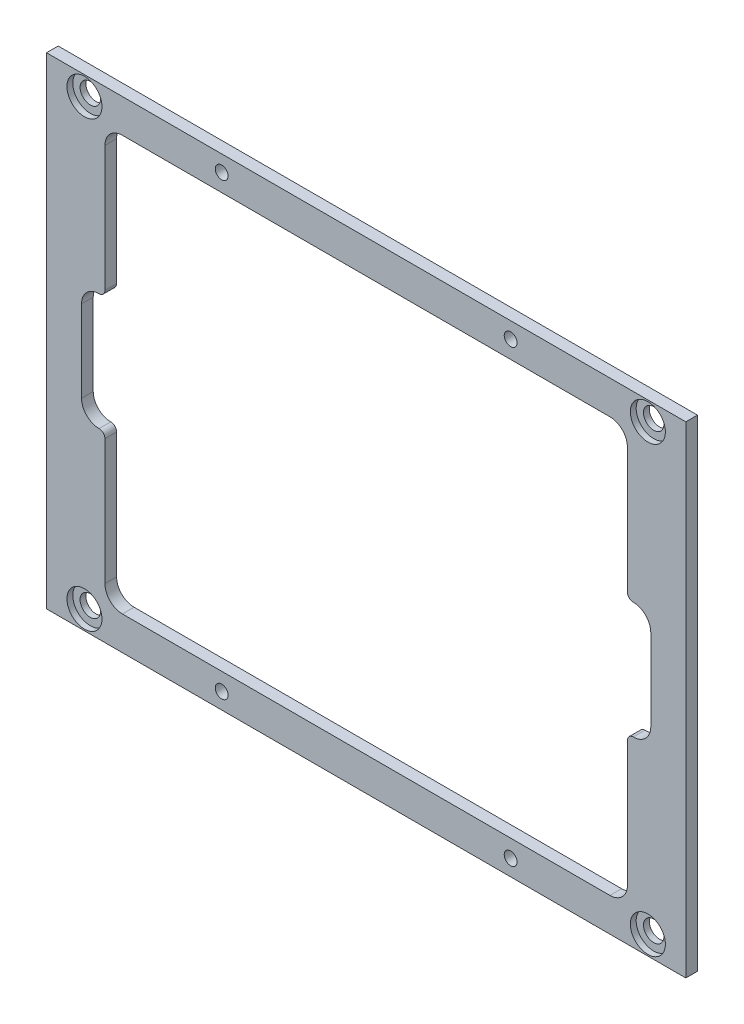
SolidWorks part; units mm, degrees
ref_plane "Front Plane" through (0, 0, 0) normal (0, 0, 1) x (1, 0, 0)
ref_plane "Top Plane" through (0, 0, 0) normal (0, 1, 0) x (1, 0, 0)
ref_plane "Right Plane" through (0, 0, 0) normal (1, 0, 0) x (0, 0, -1)
sketch "Sketch1" plane through (0, 0, 7.4347) normal (0, 0, 1) x (1, 0, 0)
  line L0 (-45.4936, 34.7019) -> (-49.4936, 34.7019)
  line L1 (-55.4936, 3.4519) -> (54.0064, 3.4519)
  line L2 (-55.4936, 3.4519) -> (-55.4936, 85.9519)
  line L3 (-55.4936, 85.9519) -> (54.0064, 85.9519)
  line L4 (54.0064, 3.4519) -> (54.0064, 85.9519)
  line L5 (55.0064, 3.4519) -> (-56.4936, 3.4519) construction
  line L6 (-49.4936, 34.7019) -> (-49.4936, 54.7019)
  line L7 (-42.4936, 80.2019) -> (41.0064, 80.2019)
  line L8 (-45.4936, 77.2019) -> (-45.4936, 54.7019)
  line L9 (-42.4936, 9.2019) -> (41.0064, 9.2019)
  line L10 (44.0064, 77.2019) -> (44.0064, 54.7019)
  line L11 (54.0064, 44.7019) -> (44.0064, 44.7019) construction
  line L12 (44.0064, 54.7019) -> (48.0064, 54.7019)
  line L13 (-55.4936, 44.7019) -> (-49.4936, 44.7019) construction
  line L14 (44.0064, 34.7019) -> (48.0064, 34.7019)
  line L15 (48.0064, 54.7019) -> (48.0064, 44.7019)
  line L16 (48.0064, 44.7019) -> (48.0064, 34.7019)
  line L17 (44.0064, 34.7019) -> (44.0064, 12.2019)
  line L18 (-49.4936, 54.7019) -> (-45.4936, 54.7019)
  line L19 (-45.4936, 34.7019) -> (-45.4936, 12.2019)
  line L20 (-45.4936, 44.7019) -> (54.0064, 44.7019) construction
  arc A0 (-45.4936, 12.2019) -> (-42.4936, 9.2019) centre (-42.4936, 12.2019) ccw
  arc A1 (41.0064, 9.2019) -> (44.0064, 12.2019) centre (41.0064, 12.2019) ccw
  arc A2 (41.0064, 80.2019) -> (44.0064, 77.2019) centre (41.0064, 77.2019) cw
  arc A3 (-42.4936, 80.2019) -> (-45.4936, 77.2019) centre (-42.4936, 77.2019) ccw
  dimension "D7" = 3
  dimension "D1" = 109.5
  dimension "D2" = 82.5
  dimension "D3" = 10
  dimension "D4" = 35.5
  dimension "D5" = 10
  dimension "D6" = 35.5
  dimension "D8" = 10
  dimension "D9" = 10
  dimension "D10" = 4
  dimension "D11" = 10
  dimension "D12" = 4
  dimension "D13" = 10
extrude "Boss-Extrude1" add sketch "Sketch1" along normal blind 2
hole_wizard "Ø3.5 (3.5) Diameter Hole1" positions "Sketch7" profile "Sketch6" hole size "Ø3.5" standard "Ansi Metric" end condition up to next
sketch "Sketch7" plane through (0, 0, 9.4347) normal (0, 0, 1) x (1, 0, 0)
  line L1 (-55.4936, 85.9519) -> (-55.4936, 3.4519) construction
  line L3 (54.0064, 3.4519) -> (54.0064, 85.9519) construction
  line L4 (-55.4936, 44.7019) -> (54.0064, 44.7019) construction
  point P0 (-48.9936, 6.7019)
  point P7 (-48.9936, 82.7019)
  point P9 (47.5064, 82.7019)
  point P11 (47.5064, 6.7019)
  dimension "D1" = 38
  dimension "D2" = 6.5
  dimension "D3" = 6.5
  dimension "D4" = 38
  dimension "D5" = 38
  dimension "D6" = 6.5
  dimension "D7" = 6.5
  dimension "D8" = 38
sketch "Sketch6" plane through (-48.9936, 6.7019, 9.4347) normal (1, 0, 0) x (0, -1, 0)
  line L0 (0, 0) -> (0, 2)
  line L1 (0, 2) -> (1.75, 2)
  line L2 (1.75, 2) -> (1.75, 0)
  line L5 (1.75, 0) -> (0, 0)
  line L11 (0, -6.35) -> (0, 107.95) construction
  dimension "Thru Hole Dia." = 3.5
  dimension "Thru Hole Depth" = 2
hole_wizard "Ø2.2 (2.2) Diameter Hole1" positions "3DSketch4" profile "Sketch11" hole size "Ø2.2" standard "Ansi Metric" end condition up to next
sketch3d "3DSketch4"
  line L1 (-55.4936, 85.9519, 9.4347) -> (-55.4936, 3.4519, 9.4347) construction
  line L2 (54.0064, 3.4519, 9.4347) -> (54.0064, 85.9519, 9.4347) construction
  line L4 (-55.4936, 44.7019, 9.4347) -> (54.0064, 44.7019, 9.4347) construction
  point P0 (-25.4936, 83.2019, 9.4347)
  point P2 (24.0064, 83.2019, 9.4347)
  point P4 (24.0064, 6.2019, 9.4347)
  point P6 (-25.4936, 6.2019, 9.4347)
  dimension "D1" = 38.5
  dimension "D2" = 30
  dimension "D3" = 38.5
  dimension "D4" = 30
  dimension "D5" = 38.5
  dimension "D6" = 30
  dimension "D7" = 38.5
  dimension "D8" = 30
sketch "Sketch11" plane through (-25.4936, 83.2019, 9.4347) normal (1, 0, 0) x (0, -1, 0)
  line L0 (0, 0) -> (0, 2)
  line L1 (0, 2) -> (1.1, 2)
  line L2 (1.1, 2) -> (1.1, 0)
  line L5 (1.1, 0) -> (0, 0)
  line L11 (0, -6.35) -> (0, 107.95) construction
  dimension "Thru Hole Dia." = 2.2
  dimension "Thru Hole Depth" = 2
sketch "Sketch12" plane through (0, 0, 9.4347) normal (0, 0, 1) x (1, 0, 0)
  circle A0 centre (-48.9936, 82.7019) radius 3
  circle A1 centre (47.5064, 82.7019) radius 3
  circle A2 centre (47.5064, 6.7019) radius 3
  circle A3 centre (-48.9936, 6.7019) radius 3
  dimension "D1" = 6
  dimension "D2" = 6
  dimension "D3" = 6
  dimension "D4" = 6
extrude "Cut-Extrude1" cut sketch "Sketch12" against normal blind 1
fillet "Fillet1" radius 3 4 edges at (48.0064, 34.7019, 8.4347) (48.0064, 54.7019, 8.4347) (-49.4936, 34.7019, 8.4347) (-49.4936, 54.7019, 8.4347)
fillet "Fillet2" radius 1 4 edges at (44.0064, 34.7019, 8.4347) (44.0064, 54.7019, 8.4347) (-45.4936, 34.7019, 8.4347) (-45.4936, 54.7019, 8.4347)
